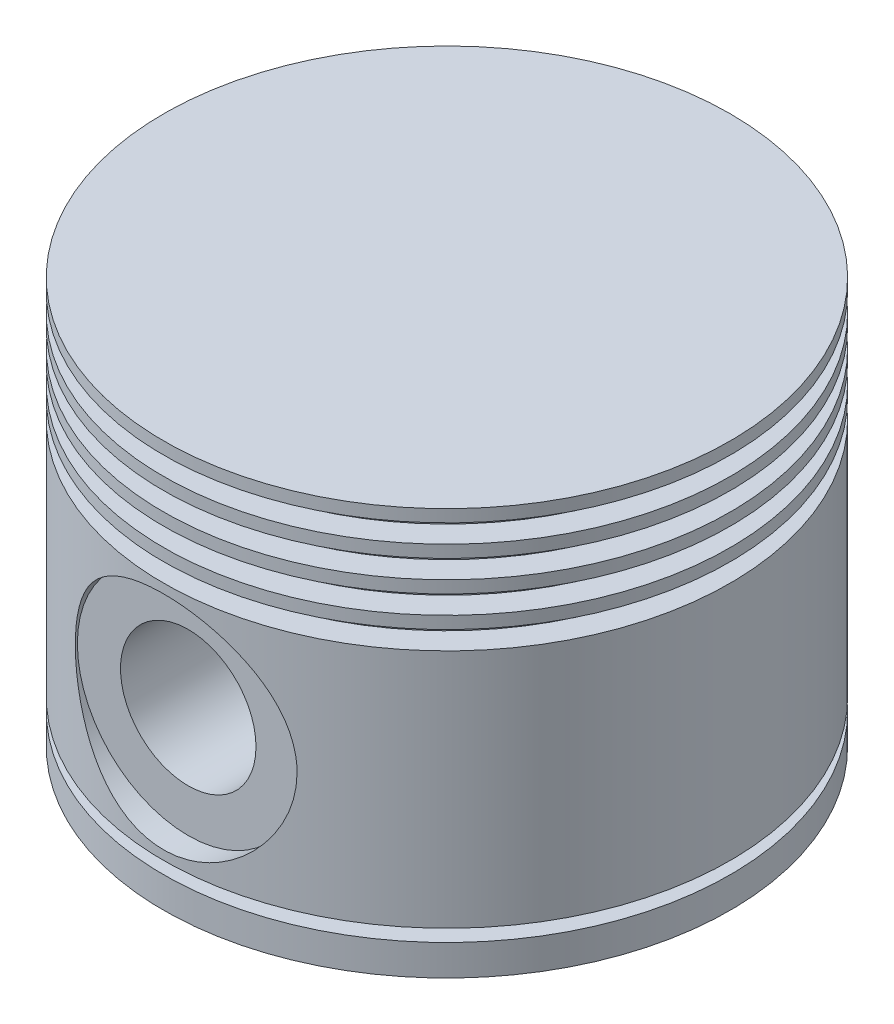
SolidWorks part; units mm, degrees
ref_plane "Front Plane" through (0, 0, 0) normal (0, 0, 1) x (1, 0, 0)
ref_plane "Top Plane" through (0, 0, 0) normal (0, 1, 0) x (1, 0, 0)
ref_plane "Right Plane" through (0, 0, 0) normal (1, 0, 0) x (0, 0, -1)
sketch "Sketch1" plane through (0, 0, 0) normal (0, 0, 1) x (1, 0, 0)
  line L0 (0, 0) -> (0, 66) construction
  line L1 (0, 66) -> (46, 66)
  line L2 (46, 66) -> (46, 64)
  line L3 (46, 64) -> (42, 64)
  line L4 (42, 64) -> (42, 61)
  line L5 (42, 61) -> (46, 61)
  line L6 (46, 61) -> (46, 59)
  line L7 (46, 59) -> (42, 59)
  line L8 (42, 59) -> (42, 56)
  line L9 (42, 56) -> (46, 56)
  line L10 (46, 56) -> (46, 54)
  line L11 (46, 54) -> (42, 54)
  line L12 (42, 54) -> (42, 51)
  line L13 (42, 51) -> (46, 51)
  line L14 (46, 51) -> (46, 49)
  line L15 (46, 49) -> (42, 49)
  line L16 (42, 49) -> (42, 46)
  line L17 (42, 46) -> (46, 46)
  line L18 (46, 46) -> (46, 7)
  line L19 (46, 7) -> (42, 7)
  line L20 (42, 7) -> (42, 5)
  line L21 (42, 5) -> (46, 5)
  line L22 (46, 5) -> (46, 0)
  line L23 (0, 0) -> (37, 0) construction
  line L24 (46, 0) -> (37, 0)
  line L25 (37, 0) -> (37, 62)
  line L26 (37, 62) -> (0, 62)
  line L27 (0, 66) -> (0, 62)
  dimension "D1" = 66
  dimension "D2" = 3
  dimension "D3" = 4
  dimension "D4" = 2
  dimension "D5" = 39
  dimension "D6" = 37
  dimension "D7" = 4
  dimension "D8" = 46
  dimension "D9" = 2
  dimension "D10" = 4
revolve "Revolve1" add sketch "Sketch1" angle 360 about L0
sketch "Sketch2" plane through (0, 0, 0) normal (0, 0, 1) x (1, 0, 0)
  line L0 (-46, 46) -> (-46, 7) construction
  line L1 (-46, 7) -> (46, 7) construction
  line L2 (46, 7) -> (46, 46) construction
  line L3 (46, 46) -> (-46, 46) construction
  line L4 (-46, 46) -> (-46, 7)
  line L5 (-46, 7) -> (46, 7)
  line L6 (46, 7) -> (46, 46)
  line L7 (46, 46) -> (-46, 46)
  line L8 (0, 46) -> (0, 7) construction
  line L9 (-46, 26.5) -> (46, 26.5) construction
  circle A0 centre (0, 26.5) radius 18
  circle A1 centre (0, 26.5) radius 11
  dimension "D1" = 36
  dimension "D2" = 22
extrude "Cut-Extrude1" cut sketch "Sketch2" against normal through all both and the other way through all contours A1 region at (0, 26.5, 0)
extrude "Boss-Extrude1" add sketch "Sketch2<3>" along normal up to body from offset 25 contours A0 A1 region at (-17.4909, 26.5, 0)
sketch "Sketch2<3>" plane through (0, 0, 0) normal (0, 0, 1) x (1, 0, 0) same geometry as "Sketch2"
extrude "Cut-Extrude3" cut sketch "Sketch2<5>" against normal blind 4 from offset 46 contours A0 A1 region at (-17.4909, 26.5, 0)
sketch "Sketch2<5>" plane through (0, 0, 0) normal (0, 0, 1) x (1, 0, 0) same geometry as "Sketch2"
mirror "Mirror1" about plane through (0, 0, 0) normal (0, 0, 1) of "Cut-Extrude3", "Boss-Extrude1"
